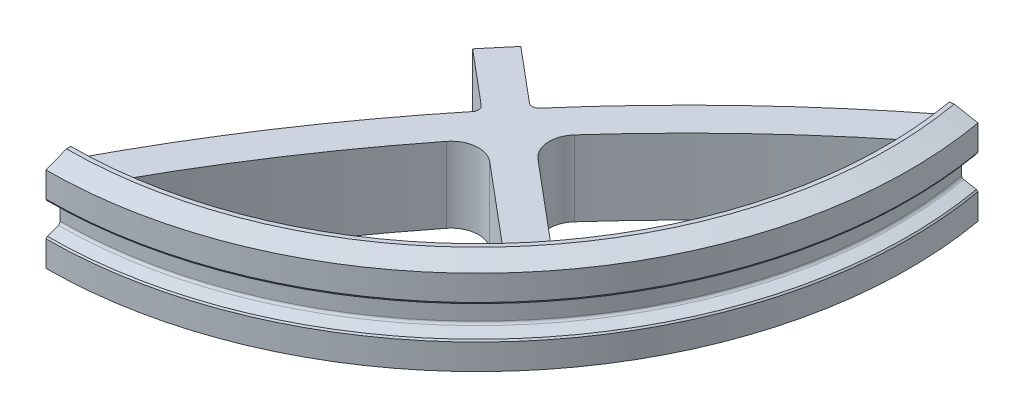
SolidWorks part; units mm, degrees
ref_plane "Front Plane" through (0, 0, 0) normal (0, 0, 1) x (1, 0, 0)
ref_plane "Top Plane" through (0, 0, 0) normal (0, 1, 0) x (1, 0, 0)
ref_plane "Right Plane" through (0, 0, 0) normal (1, 0, 0) x (0, 0, -1)
sketch "Sketch1" plane through (0, 0, 0) normal (1, 0, 0) x (0, 0, -1)
  line L0 (8.255, 9.8559) -> (8.001, 9.6019)
  line L1 (8.001, 9.6019) -> (3.3175, 9.6019)
  line L3 (3, 9.2844) -> (3, 3.3242)
  line L5 (3.2089, 3.0259) -> (5.4418, 2.2132)
  line L6 (5.4418, 2.2132) -> (5.6275, 1.8916)
  line L7 (5.6275, 1.8916) -> (5.6275, 0.254)
  line L8 (5.6275, 0.254) -> (5.3735, 0)
  line L9 (5.3735, 0) -> (0, 0)
  line L11 (0, 12.0097) -> (6.1625, 12.0097)
  line L12 (6.1625, 12.0097) -> (8.255, 10.1908)
  line L13 (8.255, 10.1908) -> (8.255, 9.8559)
  line L38 (0, 12.0097) -> (0, 0)
  line L39 (0, 6.0049) -> (83.82, 6.0049) construction
  line L40 (83.82, 6.0049) -> (83.82, 9.8559) construction
  arc A2 (3, 9.2844) -> (3.3175, 9.6019) centre (3.3175, 9.2844) cw
  arc A3 (3.2089, 3.0259) -> (3, 3.3242) centre (3.3175, 3.3242) cw
  point P16 (0, 0)
  point P19 (0, -12.0097)
  point P31 (0, 0)
  dimension "D1" = 0.3175
  dimension "D2" = 3
  dimension "D3" = 3.2089
  dimension "D4" = 5.3735
  dimension "D5" = 5.4418
  dimension "D6" = 5.6275
  dimension "D7" = 6.1625
  dimension "D8" = 8.001
  dimension "D9" = 8.255
  dimension "D10" = 83.82
  dimension "D11" = 0.254
  dimension "D12" = 1.8916
  dimension "D13" = 2.2132
  dimension "D14" = 6.0049
  dimension "D15" = 9.6019
  dimension "D19" = 10.1908
sketch "Sketch2" plane through (0, 0, 0) normal (1, 0, 0) x (0, 0, -1)
  line L0 (8.3044, 9.4019) -> (7.5034, 9.4019)
  line L1 (7.5034, 9.4019) -> (3.7034, 7.9019)
  line L2 (3.7034, 7.9019) -> (3.7034, 3.2103)
  line L3 (3.7034, 3.2103) -> (3.889, 2.8888)
  line L4 (3.889, 2.8888) -> (5.9966, 2.1217)
  line L5 (6.3309, 1.6443) -> (6.3309, -1.6443)
  line L6 (5.9966, -2.1217) -> (3.942, -2.8695)
  line L7 (3.942, -2.8695) -> (3.7034, -3.1539)
  line L8 (3.7034, -3.1539) -> (3.7034, -7.9019)
  line L9 (3.7034, -7.9019) -> (7.5034, -9.4019)
  line L10 (7.5034, -9.4019) -> (8.3044, -9.4019)
  line L11 (8.3044, -9.4019) -> (8.3044, 9.4019)
  arc A0 (6.3309, 1.6443) -> (5.9966, 2.1217) centre (5.8229, 1.6443) ccw
  arc A1 (5.9966, -2.1217) -> (6.3309, -1.6443) centre (5.8229, -1.6443) ccw
  dimension "D1" = 0.508
  dimension "D2" = 3.7034
  dimension "D3" = 3.889
  dimension "D4" = 3.942
  dimension "D5" = 5.8229
  dimension "D6" = 5.9966
  dimension "D7" = 1.6443
  dimension "D8" = 7.5034
  dimension "D9" = 8.3044
  dimension "D10" = 3.2103
  dimension "D11" = 7.9019
  dimension "D12" = 9.4019
  dimension "D13" = 1.6443
  dimension "D14" = 7.9019
ref_axis "Axis1" through (0, 6.0049, -83.82) along (0, 1, 0)
revolve "Revolve5" add sketch "Sketch2" angle 100 about axis through (0, 6.0049, -83.82) along (0, 1, 0)
sketch "Sketch3" plane through (0, 0, 0) normal (0, 1, 0) x (1, 0, 0)
  line L0 (0, 83.82) -> (61.3729, 32.322) construction
  line L1 (-8.509, 92.329) -> (8.509, 92.329) construction
  line L2 (-8.509, 92.329) -> (-8.509, 75.311) construction
  line L3 (-8.509, 75.311) -> (8.509, 75.311) construction
  line L4 (8.509, 92.329) -> (8.509, 75.311) construction
  line L5 (-8.509, 92.329) -> (8.509, 75.311) construction
  line L6 (-8.509, 75.311) -> (8.509, 92.329) construction
  line L7 (78.8995, 97.7321) -> (0, 83.82) construction
  circle A0 centre (0, 83.82) radius 6.35 construction
  circle A1 centre (0, 83.82) radius 12.0335 construction
  arc A2 (0, 3.7034) -> (78.8995, 97.7321) centre (0, 83.82) ccw construction
  point P0 (0, 83.82)
  dimension "D1" = 17.018
  dimension "D2" = 17.018
sketch "Sketch4" plane through (0, 0, 0) normal (0, 1, 0) x (1, 0, 0)
  line L1 (0, 7.5034) -> (7.3823, 7.8613)
  line L3 (56.3705, 32.3749) -> (60.4522, 37.2393)
  line L4 (33.8099, 59.5948) -> (23.9075, 67.9039)
  line L5 (30.6734, 53.9373) -> (30.6876, 53.9254)
  line L6 (2.0409, 86.2522) -> (63.4138, 34.7542)
  line L7 (34.7551, 58.8017) -> (34.7693, 58.7898)
  line L8 (29.7282, 54.7304) -> (19.8258, 63.0395)
  line L9 (19.8258, 63.0395) -> (23.9075, 67.9039)
  line L12 (75.1572, 97.0722) -> (76.0867, 89.74)
  line L13 (39.5293, 46.5063) -> (56.3705, 32.3749)
  line L14 (43.611, 51.3707) -> (60.4522, 37.2393)
  arc A0 (0, 7.5034) -> (29.8978, 52.9571) centre (241.3027, -118.657) cw
  arc A1 (0, 7.5034) -> (75.1572, 97.0722) centre (0, 83.82) ccw construction
  arc A2 (7.3823, 7.8613) -> (32.2711, 45.7553) centre (241.3027, -118.657) cw
  arc A3 (5.6273, 4.5612) -> (79.0318, 92.0413) centre (241.3027, -118.657) cw construction
  arc A4 (43.0902, 58.649) -> (76.0867, 89.74) centre (241.3027, -118.657) cw
  arc A5 (35.5857, 59.7357) -> (75.1572, 97.0722) centre (241.3027, -118.657) cw
  arc A6 (0, 7.5034) -> (75.1572, 97.0722) centre (241.3027, -118.657) cw construction
  arc A7 (29.7282, 54.7304) -> (29.8978, 52.9571) centre (28.9118, 53.7576) cw
  arc A8 (35.5857, 59.7357) -> (33.8099, 59.5948) centre (34.6262, 60.5677) cw
  arc A9 (39.5293, 46.5063) -> (32.2711, 45.7553) centre (36.264, 42.6148) ccw
  arc A10 (43.611, 51.3707) -> (43.0902, 58.649) centre (46.8764, 55.2622) cw
  dimension "D5" = 1.27
  dimension "D6" = 1.27
  dimension "D7" = 5.08
  dimension "D8" = 5.08
  dimension "D3" = 3.175
  dimension "D4" = 6.35
extrude "Boss-Extrude1" add sketch "Sketch4" along normal blind 7.62 and the other way blind 6.35 contours A5 L12 A4 A10 L14 L3 L13 A9 A2 L1 A0 A7 L8 L9 L4 A8
